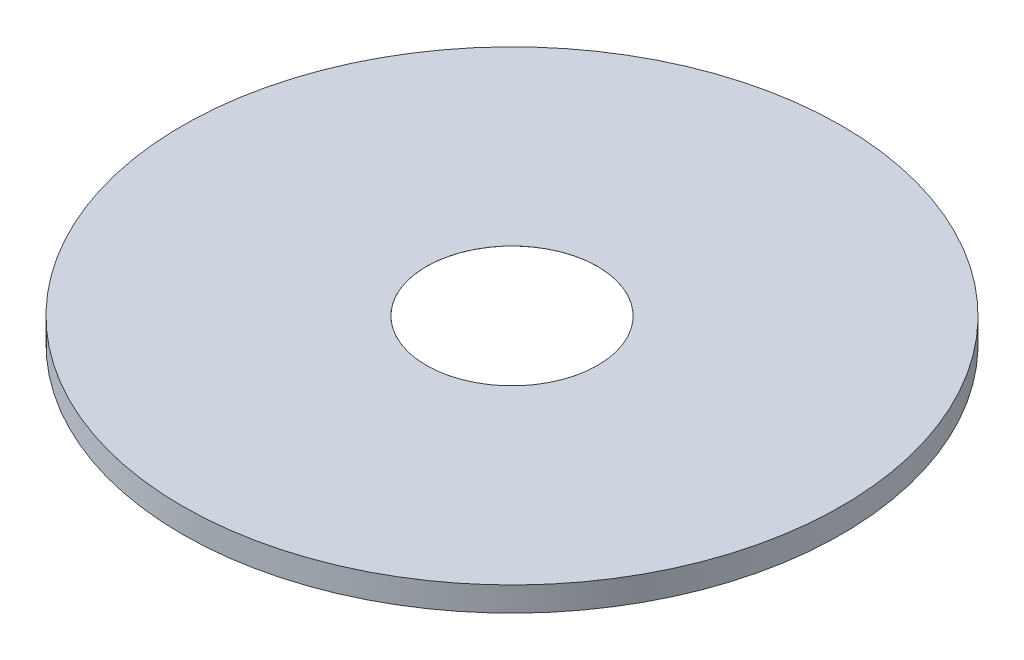
SolidWorks part; units mm, degrees
material "6061 Alloy"
ref_plane "Front Plane" through (0, 0, 0) normal (0, 0, 1) x (1, 0, 0)
ref_plane "Top Plane" through (0, 0, 0) normal (0, 1, 0) x (1, 0, 0)
ref_plane "Right Plane" through (0, 0, 0) normal (1, 0, 0) x (0, 0, -1)
sketch "Sketch1" plane through (0, 0, 0) normal (0, 1, 0) x (1, 0, 0)
  circle A0 centre (0, 0) radius 13.5
  circle A1 centre (0, 0) radius 3.51
  dimension "D1" = 27
  dimension "D2" = 7.02
extrude "Boss-Extrude1" add sketch "Sketch1" along normal blind 1
sketch "Sketch2" plane through (0, 0, 0) normal (1, 0, 0) x (0, 0, -1)
  line L0 (-3.505, 1) -> (-5.2984, 0)
  line L1 (13.5, 1) -> (-13.5, 1) construction
  line L2 (3.51, 1) -> (-3.51, 1) construction
  line L3 (-13.5, 0) -> (13.5, 0) construction
  line L4 (-5.2984, 0) -> (-3.505, 0)
  line L5 (-3.51, 0) -> (3.51, 0) construction
  line L6 (-3.505, 0) -> (-3.505, 1)
  line L7 (0, -2.0608) -> (0, 5.8713) construction
  dimension "D1" = 2.0534
  dimension "D2" = 3.505
revolve "Cut-Revolve1" cut sketch "Sketch2" angle 360 about L7
